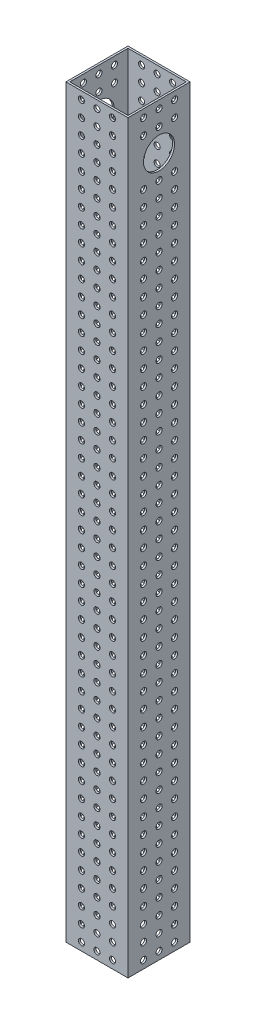
SolidWorks part; units mm, degrees
ref_plane "Front Plane" through (0, 0, 0) normal (0, 0, 1) x (1, 0, 0)
ref_plane "Top Plane" through (0, 0, 0) normal (0, 1, 0) x (1, 0, 0)
ref_plane "Right Plane" through (0, 0, 0) normal (1, 0, 0) x (0, 0, -1)
sketch "Sketch1" plane through (0, 0, 0) normal (0, 1, 0) x (1, 0, 0)
  line L1 (-25.4, 25.4) -> (25.4, 25.4)
  line L2 (-25.4, 25.4) -> (-25.4, -25.4)
  line L3 (-25.4, -25.4) -> (25.4, -25.4)
  line L4 (25.4, 25.4) -> (25.4, -25.4)
  line L5 (-25.4, 25.4) -> (25.4, -25.4) construction
  line L6 (-25.4, -25.4) -> (25.4, 25.4) construction
  line L7 (23.8125, 23.8125) -> (-23.8125, 23.8125)
  line L8 (23.8125, 23.8125) -> (23.8125, -23.8125)
  line L9 (23.8125, -23.8125) -> (-23.8125, -23.8125)
  line L10 (-23.8125, 23.8125) -> (-23.8125, -23.8125)
  line L11 (23.8125, 23.8125) -> (-23.8125, -23.8125) construction
  line L12 (23.8125, -23.8125) -> (-23.8125, 23.8125) construction
  point P0 (0, 0)
  point P6 (0, 0)
  dimension "D1" = 50.8
  dimension "D2" = 50.8
  dimension "D3" = 1.5875
  dimension "D4" = 1.5875
extrude "Boss-Extrude1" add sketch "Sketch1" along normal blind 685.8
sketch "Sketch2" plane through (0, 0, 25.4) normal (0, 0, 1) x (1, 0, 0)
  line L0 (0, 685.8) -> (0, 0) construction
  line L1 (-25.4, 685.8) -> (25.4, 685.8) construction
  line L2 (-25.4, 685.8) -> (-25.4, 0) construction
  line L3 (-6.35, 685.8) -> (-6.35, 0) construction
  line L5 (-25.4, 0) -> (25.4, 0) construction
  circle A0 centre (-12.7, 679.45) radius 2.4892
  circle A1 centre (-12.7, 666.75) radius 2.4892
  circle A2 centre (-12.7, 654.05) radius 2.4892
  circle A3 centre (-12.7, 641.35) radius 2.4892
  circle A4 centre (-12.7, 628.65) radius 2.4892
  circle A5 centre (-12.7, 615.95) radius 2.4892
  circle A6 centre (-12.7, 603.25) radius 2.4892
  circle A7 centre (-12.7, 590.55) radius 2.4892
  circle A8 centre (-12.7, 577.85) radius 2.4892
  circle A9 centre (-12.7, 565.15) radius 2.4892
  circle A10 centre (-12.7, 552.45) radius 2.4892
  circle A11 centre (-12.7, 539.75) radius 2.4892
  circle A12 centre (-12.7, 527.05) radius 2.4892
  circle A13 centre (-12.7, 514.35) radius 2.4892
  circle A14 centre (-12.7, 501.65) radius 2.4892
  circle A15 centre (-12.7, 488.95) radius 2.4892
  circle A16 centre (-12.7, 476.25) radius 2.4892
  circle A17 centre (-12.7, 463.55) radius 2.4892
  circle A18 centre (-12.7, 450.85) radius 2.4892
  circle A19 centre (-12.7, 438.15) radius 2.4892
  circle A20 centre (-12.7, 425.45) radius 2.4892
  circle A21 centre (-12.7, 412.75) radius 2.4892
  circle A22 centre (-12.7, 400.05) radius 2.4892
  circle A23 centre (-12.7, 387.35) radius 2.4892
  circle A24 centre (-12.7, 374.65) radius 2.4892
  circle A25 centre (-12.7, 361.95) radius 2.4892
  circle A26 centre (-12.7, 349.25) radius 2.4892
  circle A27 centre (-12.7, 336.55) radius 2.4892
  circle A28 centre (-12.7, 323.85) radius 2.4892
  circle A29 centre (-12.7, 311.15) radius 2.4892
  circle A30 centre (-12.7, 298.45) radius 2.4892
  circle A31 centre (-12.7, 285.75) radius 2.4892
  circle A32 centre (-12.7, 273.05) radius 2.4892
  circle A33 centre (-12.7, 260.35) radius 2.4892
  circle A34 centre (-12.7, 247.65) radius 2.4892
  circle A35 centre (-12.7, 234.95) radius 2.4892
  circle A36 centre (-12.7, 222.25) radius 2.4892
  circle A37 centre (-12.7, 209.55) radius 2.4892
  circle A38 centre (-12.7, 196.85) radius 2.4892
  circle A39 centre (-12.7, 184.15) radius 2.4892
  circle A40 centre (-12.7, 171.45) radius 2.4892
  circle A41 centre (-12.7, 158.75) radius 2.4892
  circle A42 centre (-12.7, 146.05) radius 2.4892
  circle A43 centre (-12.7, 133.35) radius 2.4892
  circle A44 centre (-12.7, 120.65) radius 2.4892
  circle A45 centre (-12.7, 107.95) radius 2.4892
  circle A46 centre (-12.7, 95.25) radius 2.4892
  circle A47 centre (-12.7, 82.55) radius 2.4892
  circle A48 centre (-12.7, 69.85) radius 2.4892
  circle A49 centre (-12.7, 57.15) radius 2.4892
  circle A50 centre (-12.7, 44.45) radius 2.4892
  circle A51 centre (-12.7, 31.75) radius 2.4892
  circle A52 centre (-12.7, 19.05) radius 2.4892
  circle A53 centre (-12.7, 6.35) radius 2.4892
  circle A54 centre (12.7, 6.35) radius 2.4892
  circle A55 centre (12.7, 19.05) radius 2.4892
  circle A56 centre (12.7, 31.75) radius 2.4892
  circle A57 centre (12.7, 44.45) radius 2.4892
  circle A58 centre (12.7, 57.15) radius 2.4892
  circle A59 centre (12.7, 69.85) radius 2.4892
  circle A60 centre (12.7, 82.55) radius 2.4892
  circle A61 centre (12.7, 95.25) radius 2.4892
  circle A62 centre (12.7, 107.95) radius 2.4892
  circle A63 centre (12.7, 120.65) radius 2.4892
  circle A64 centre (12.7, 133.35) radius 2.4892
  circle A65 centre (12.7, 146.05) radius 2.4892
  circle A66 centre (12.7, 158.75) radius 2.4892
  circle A67 centre (12.7, 171.45) radius 2.4892
  circle A68 centre (12.7, 184.15) radius 2.4892
  circle A69 centre (12.7, 196.85) radius 2.4892
  circle A70 centre (12.7, 209.55) radius 2.4892
  circle A71 centre (12.7, 222.25) radius 2.4892
  circle A72 centre (12.7, 234.95) radius 2.4892
  circle A73 centre (12.7, 247.65) radius 2.4892
  circle A74 centre (12.7, 260.35) radius 2.4892
  circle A75 centre (12.7, 273.05) radius 2.4892
  circle A76 centre (12.7, 285.75) radius 2.4892
  circle A77 centre (12.7, 298.45) radius 2.4892
  circle A78 centre (12.7, 311.15) radius 2.4892
  circle A79 centre (12.7, 323.85) radius 2.4892
  circle A80 centre (12.7, 336.55) radius 2.4892
  circle A81 centre (12.7, 374.65) radius 2.4892
  circle A82 centre (12.7, 361.95) radius 2.4892
  circle A83 centre (12.7, 349.25) radius 2.4892
  circle A84 centre (12.7, 387.35) radius 2.4892
  circle A85 centre (12.7, 400.05) radius 2.4892
  circle A86 centre (12.7, 412.75) radius 2.4892
  circle A87 centre (12.7, 425.45) radius 2.4892
  circle A88 centre (12.7, 438.15) radius 2.4892
  circle A89 centre (12.7, 450.85) radius 2.4892
  circle A90 centre (12.7, 463.55) radius 2.4892
  circle A91 centre (12.7, 476.25) radius 2.4892
  circle A92 centre (12.7, 488.95) radius 2.4892
  circle A93 centre (12.7, 501.65) radius 2.4892
  circle A94 centre (12.7, 514.35) radius 2.4892
  circle A95 centre (12.7, 527.05) radius 2.4892
  circle A96 centre (12.7, 539.75) radius 2.4892
  circle A97 centre (12.7, 552.45) radius 2.4892
  circle A98 centre (12.7, 565.15) radius 2.4892
  circle A99 centre (12.7, 577.85) radius 2.4892
  circle A100 centre (12.7, 590.55) radius 2.4892
  circle A101 centre (12.7, 603.25) radius 2.4892
  circle A102 centre (12.7, 615.95) radius 2.4892
  circle A103 centre (12.7, 628.65) radius 2.4892
  circle A104 centre (12.7, 641.35) radius 2.4892
  circle A105 centre (12.7, 654.05) radius 2.4892
  circle A106 centre (12.7, 666.75) radius 2.4892
  circle A107 centre (12.7, 679.45) radius 2.4892
  circle A108 centre (0, 6.35) radius 2.4892
  circle A109 centre (0, 19.05) radius 2.4892
  circle A110 centre (0, 31.75) radius 2.4892
  circle A111 centre (0, 44.45) radius 2.4892
  circle A112 centre (0, 57.15) radius 2.4892
  circle A113 centre (0, 69.85) radius 2.4892
  circle A114 centre (0, 82.55) radius 2.4892
  circle A115 centre (0, 95.25) radius 2.4892
  circle A116 centre (0, 107.95) radius 2.4892
  circle A117 centre (0, 120.65) radius 2.4892
  circle A118 centre (0, 133.35) radius 2.4892
  circle A119 centre (0, 146.05) radius 2.4892
  circle A120 centre (0, 158.75) radius 2.4892
  circle A121 centre (0, 171.45) radius 2.4892
  circle A122 centre (0, 184.15) radius 2.4892
  circle A123 centre (0, 196.85) radius 2.4892
  circle A124 centre (0, 209.55) radius 2.4892
  circle A125 centre (0, 222.25) radius 2.4892
  circle A126 centre (0, 234.95) radius 2.4892
  circle A127 centre (0, 247.65) radius 2.4892
  circle A128 centre (0, 260.35) radius 2.4892
  circle A129 centre (0, 273.05) radius 2.4892
  circle A130 centre (0, 285.75) radius 2.4892
  circle A131 centre (0, 298.45) radius 2.4892
  circle A132 centre (0, 311.15) radius 2.4892
  circle A133 centre (0, 323.85) radius 2.4892
  circle A134 centre (0, 336.55) radius 2.4892
  circle A135 centre (0, 349.25) radius 2.4892
  circle A136 centre (0, 361.95) radius 2.4892
  circle A137 centre (0, 374.65) radius 2.4892
  circle A138 centre (0, 387.35) radius 2.4892
  circle A139 centre (0, 400.05) radius 2.4892
  circle A140 centre (0, 412.75) radius 2.4892
  circle A141 centre (0, 425.45) radius 2.4892
  circle A142 centre (0, 438.15) radius 2.4892
  circle A143 centre (0, 450.85) radius 2.4892
  circle A144 centre (0, 463.55) radius 2.4892
  circle A145 centre (0, 476.25) radius 2.4892
  circle A146 centre (0, 488.95) radius 2.4892
  circle A147 centre (0, 501.65) radius 2.4892
  circle A148 centre (0, 514.35) radius 2.4892
  circle A149 centre (0, 527.05) radius 2.4892
  circle A150 centre (0, 539.75) radius 2.4892
  circle A151 centre (0, 552.45) radius 2.4892
  circle A152 centre (0, 565.15) radius 2.4892
  circle A153 centre (0, 577.85) radius 2.4892
  circle A154 centre (0, 590.55) radius 2.4892
  circle A155 centre (0, 603.25) radius 2.4892
  circle A156 centre (0, 615.95) radius 2.4892
  circle A157 centre (0, 628.65) radius 2.4892
  circle A158 centre (0, 641.35) radius 2.4892
  circle A159 centre (0, 654.05) radius 2.4892
  circle A160 centre (0, 666.75) radius 2.4892
  circle A161 centre (0, 679.45) radius 2.4892
  dimension "D1" = 4.9784
  dimension "D2" = 6.35
  dimension "D3" = 12.7
  dimension "D5" = 12.7
  dimension "D6" = 6.35
  dimension "D4" = 54
extrude "Cut-Extrude1" cut sketch "Sketch2" against normal through all
sketch "Sketch4" plane through (25.4, 0, 0) normal (1, 0, 0) x (0, 0, -1)
  line L0 (0, 685.8) -> (0, 0) construction
  line L1 (-25.4, 685.8) -> (25.4, 685.8) construction
  line L2 (-25.4, 685.8) -> (-25.4, 0) construction
  line L3 (-6.35, -314.2) -> (-6.35, 49685.8) construction
  line L4 (25.4, 584.2) -> (-25.4, 584.2) construction
  line L5 (25.4, 685.8) -> (25.4, 0) construction
  circle A0 centre (-12.7, 679.45) radius 2.4892
  circle A1 centre (-12.7, 666.75) radius 2.4892
  circle A2 centre (-12.7, 654.05) radius 2.4892
  circle A3 centre (-12.7, 641.35) radius 2.4892
  circle A4 centre (-12.7, 628.65) radius 2.4892
  circle A5 centre (-12.7, 615.95) radius 2.4892
  circle A6 centre (-12.7, 603.25) radius 2.4892
  circle A7 centre (-12.7, 590.55) radius 2.4892
  circle A10 centre (-12.7, 552.45) radius 2.4892
  circle A11 centre (-12.7, 539.75) radius 2.4892
  circle A12 centre (-12.7, 527.05) radius 2.4892
  circle A13 centre (-12.7, 514.35) radius 2.4892
  circle A14 centre (-12.7, 501.65) radius 2.4892
  circle A15 centre (-12.7, 488.95) radius 2.4892
  circle A16 centre (-12.7, 476.25) radius 2.4892
  circle A17 centre (-12.7, 463.55) radius 2.4892
  circle A18 centre (-12.7, 450.85) radius 2.4892
  circle A19 centre (-12.7, 438.15) radius 2.4892
  circle A20 centre (-12.7, 425.45) radius 2.4892
  circle A21 centre (-12.7, 412.75) radius 2.4892
  circle A22 centre (-12.7, 400.05) radius 2.4892
  circle A23 centre (-12.7, 387.35) radius 2.4892
  circle A24 centre (-12.7, 374.65) radius 2.4892
  circle A25 centre (-12.7, 361.95) radius 2.4892
  circle A26 centre (-12.7, 349.25) radius 2.4892
  circle A27 centre (-12.7, 336.55) radius 2.4892
  circle A28 centre (-12.7, 323.85) radius 2.4892
  circle A29 centre (-12.7, 311.15) radius 2.4892
  circle A30 centre (-12.7, 298.45) radius 2.4892
  circle A31 centre (-12.7, 285.75) radius 2.4892
  circle A32 centre (-12.7, 273.05) radius 2.4892
  circle A33 centre (-12.7, 260.35) radius 2.4892
  circle A34 centre (-12.7, 247.65) radius 2.4892
  circle A35 centre (-12.7, 234.95) radius 2.4892
  circle A36 centre (-12.7, 222.25) radius 2.4892
  circle A37 centre (-12.7, 209.55) radius 2.4892
  circle A38 centre (-12.7, 196.85) radius 2.4892
  circle A39 centre (-12.7, 184.15) radius 2.4892
  circle A40 centre (-12.7, 171.45) radius 2.4892
  circle A41 centre (-12.7, 158.75) radius 2.4892
  circle A42 centre (-12.7, 146.05) radius 2.4892
  circle A43 centre (-12.7, 133.35) radius 2.4892
  circle A44 centre (-12.7, 120.65) radius 2.4892
  circle A45 centre (-12.7, 107.95) radius 2.4892
  circle A46 centre (-12.7, 95.25) radius 2.4892
  circle A47 centre (-12.7, 82.55) radius 2.4892
  circle A48 centre (-12.7, 69.85) radius 2.4892
  circle A49 centre (-12.7, 57.15) radius 2.4892
  circle A50 centre (-12.7, 44.45) radius 2.4892
  circle A51 centre (-12.7, 31.75) radius 2.4892
  circle A52 centre (-12.7, 19.05) radius 2.4892
  circle A53 centre (-12.7, 6.35) radius 2.4892
  circle A54 centre (12.7, 273.05) radius 2.4892
  circle A55 centre (12.7, 285.75) radius 2.4892
  circle A56 centre (12.7, 298.45) radius 2.4892
  circle A57 centre (12.7, 311.15) radius 2.4892
  circle A58 centre (12.7, 323.85) radius 2.4892
  circle A59 centre (12.7, 336.55) radius 2.4892
  circle A60 centre (12.7, 349.25) radius 2.4892
  circle A61 centre (12.7, 361.95) radius 2.4892
  circle A62 centre (12.7, 374.65) radius 2.4892
  circle A63 centre (12.7, 387.35) radius 2.4892
  circle A64 centre (12.7, 400.05) radius 2.4892
  circle A65 centre (12.7, 412.75) radius 2.4892
  circle A66 centre (12.7, 425.45) radius 2.4892
  circle A67 centre (12.7, 438.15) radius 2.4892
  circle A68 centre (12.7, 450.85) radius 2.4892
  circle A69 centre (12.7, 463.55) radius 2.4892
  circle A70 centre (12.7, 476.25) radius 2.4892
  circle A71 centre (12.7, 488.95) radius 2.4892
  circle A72 centre (12.7, 501.65) radius 2.4892
  circle A73 centre (12.7, 514.35) radius 2.4892
  circle A74 centre (12.7, 527.05) radius 2.4892
  circle A75 centre (12.7, 539.75) radius 2.4892
  circle A76 centre (12.7, 552.45) radius 2.4892
  circle A79 centre (12.7, 590.55) radius 2.4892
  circle A80 centre (12.7, 603.25) radius 2.4892
  circle A81 centre (12.7, 615.95) radius 2.4892
  circle A82 centre (12.7, 628.65) radius 2.4892
  circle A83 centre (12.7, 641.35) radius 2.4892
  circle A84 centre (12.7, 654.05) radius 2.4892
  circle A85 centre (12.7, 666.75) radius 2.4892
  circle A86 centre (12.7, 19.05) radius 2.4892
  circle A87 centre (12.7, 31.75) radius 2.4892
  circle A88 centre (12.7, 44.45) radius 2.4892
  circle A89 centre (12.7, 57.15) radius 2.4892
  circle A90 centre (12.7, 69.85) radius 2.4892
  circle A91 centre (12.7, 82.55) radius 2.4892
  circle A92 centre (12.7, 95.25) radius 2.4892
  circle A93 centre (12.7, 107.95) radius 2.4892
  circle A94 centre (12.7, 120.65) radius 2.4892
  circle A95 centre (12.7, 133.35) radius 2.4892
  circle A96 centre (12.7, 146.05) radius 2.4892
  circle A97 centre (12.7, 158.75) radius 2.4892
  circle A98 centre (12.7, 171.45) radius 2.4892
  circle A99 centre (12.7, 184.15) radius 2.4892
  circle A100 centre (12.7, 196.85) radius 2.4892
  circle A101 centre (12.7, 209.55) radius 2.4892
  circle A102 centre (12.7, 222.25) radius 2.4892
  circle A103 centre (12.7, 234.95) radius 2.4892
  circle A104 centre (12.7, 247.65) radius 2.4892
  circle A105 centre (12.7, 260.35) radius 2.4892
  circle A106 centre (12.7, 6.35) radius 2.4892
  circle A107 centre (12.7, 679.45) radius 2.4892
  circle A108 centre (0, 6.35) radius 2.4892
  circle A109 centre (0, 19.05) radius 2.4892
  circle A110 centre (0, 31.75) radius 2.4892
  circle A111 centre (0, 44.45) radius 2.4892
  circle A112 centre (0, 57.15) radius 2.4892
  circle A113 centre (0, 69.85) radius 2.4892
  circle A114 centre (0, 82.55) radius 2.4892
  circle A115 centre (0, 95.25) radius 2.4892
  circle A116 centre (0, 107.95) radius 2.4892
  circle A117 centre (0, 120.65) radius 2.4892
  circle A118 centre (0, 133.35) radius 2.4892
  circle A119 centre (0, 146.05) radius 2.4892
  circle A120 centre (0, 158.75) radius 2.4892
  circle A121 centre (0, 171.45) radius 2.4892
  circle A122 centre (0, 184.15) radius 2.4892
  circle A123 centre (0, 196.85) radius 2.4892
  circle A124 centre (0, 209.55) radius 2.4892
  circle A125 centre (0, 222.25) radius 2.4892
  circle A126 centre (0, 234.95) radius 2.4892
  circle A127 centre (0, 247.65) radius 2.4892
  circle A128 centre (0, 260.35) radius 2.4892
  circle A129 centre (0, 273.05) radius 2.4892
  circle A130 centre (0, 285.75) radius 2.4892
  circle A131 centre (0, 298.45) radius 2.4892
  circle A132 centre (0, 311.15) radius 2.4892
  circle A133 centre (0, 323.85) radius 2.4892
  circle A134 centre (0, 336.55) radius 2.4892
  circle A135 centre (0, 349.25) radius 2.4892
  circle A136 centre (0, 361.95) radius 2.4892
  circle A137 centre (0, 374.65) radius 2.4892
  circle A138 centre (0, 387.35) radius 2.4892
  circle A139 centre (0, 400.05) radius 2.4892
  circle A140 centre (0, 412.75) radius 2.4892
  circle A141 centre (0, 425.45) radius 2.4892
  circle A142 centre (0, 438.15) radius 2.4892
  circle A143 centre (0, 450.85) radius 2.4892
  circle A144 centre (0, 463.55) radius 2.4892
  circle A145 centre (0, 476.25) radius 2.4892
  circle A146 centre (0, 488.95) radius 2.4892
  circle A147 centre (0, 501.65) radius 2.4892
  circle A148 centre (0, 514.35) radius 2.4892
  circle A149 centre (0, 527.05) radius 2.4892
  circle A150 centre (0, 539.75) radius 2.4892
  circle A151 centre (0, 552.45) radius 2.4892
  circle A154 centre (0, 590.55) radius 2.4892
  circle A155 centre (0, 603.25) radius 2.4892
  circle A156 centre (0, 615.95) radius 2.4892
  circle A157 centre (0, 628.65) radius 2.4892
  circle A158 centre (0, 641.35) radius 2.4892
  circle A159 centre (0, 654.05) radius 2.4892
  circle A160 centre (0, 666.75) radius 2.4892
  circle A161 centre (0, 679.45) radius 2.4892
  circle A162 centre (-12.7, 565.15) radius 2.4892 [skipped]
  circle A163 centre (-12.7, 577.85) radius 2.4892 [skipped]
  dimension "D1" = 4.9784
  dimension "D2" = 12.7
  dimension "D3" = 6.35
  dimension "D5" = 12.7
  dimension "D6" = 6.35
  dimension "D7" = 101.6
  dimension "D4" = 54
extrude "Cut-Extrude2" cut sketch "Sketch4" against normal through all
sketch "Sketch5" plane through (25.4, 0, 0) normal (1, 0, 0) x (0, 0, -1)
  line L0 (25.4, 685.8) -> (25.4, 0) construction
  line L1 (25.4, 609.6) -> (-25.4, 609.6)
  line L6 (-25.4, 685.8) -> (25.4, 685.8)
  line L7 (-25.4, 685.8) -> (-25.4, 609.6)
  line L8 (-25.4, 609.6) -> (25.4, 609.6)
  line L9 (25.4, 685.8) -> (25.4, 609.6)
  dimension "D1" = 50.8
  dimension "D2" = 76.2
  dimension "D3" = 76.2
extrude "Cut-Extrude3" cut sketch "Sketch5" against normal through all contours L9 L6 L7 L1 region at (25.4, 647.7, 0)
sketch "Sketch6" plane through (25.4, 0, 0) normal (1, 0, 0) x (0, 0, -1)
  line L0 (0, 609.6) -> (0, 0) construction
  line L1 (25.4, 609.6) -> (-25.4, 609.6) construction
  circle A0 centre (0, 571.9064) radius 12.7
  dimension "D2" = 25.4
  dimension "D1" = 37.6936
extrude "Cut-Extrude4" cut sketch "Sketch6" against normal through all
